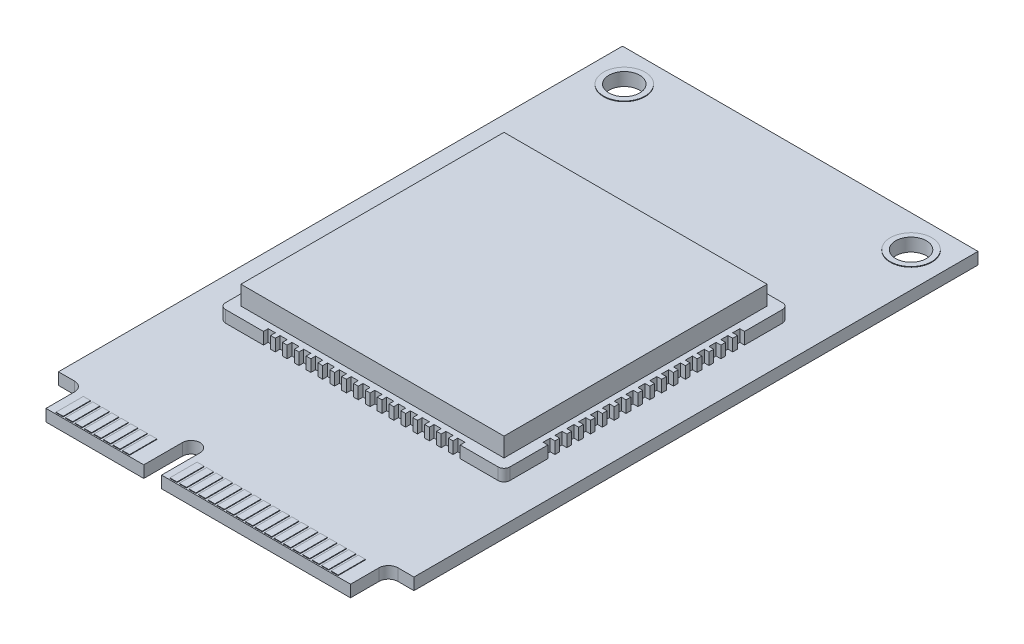
SolidWorks part; units mm, degrees
ref_plane "Front Plane" through (0, 0, 0) normal (0, 0, 1) x (1, 0, 0)
ref_plane "Top Plane" through (0, 0, 0) normal (0, 1, 0) x (1, 0, 0)
ref_plane "Right Plane" through (0, 0, 0) normal (1, 0, 0) x (0, 0, -1)
sketch "Sketch1" plane through (0, 0, 0) normal (0, 1, 0) x (1, 0, 0)
  line L0 (0, 23.8) -> (0, -48.0579) construction
  line L1 (-15, -23.8) -> (-13.65, -23.8)
  line L2 (-15, -23.8) -> (-15, 23.8)
  line L3 (-15, 23.8) -> (15, 23.8)
  line L4 (15, -23.8) -> (15, 23.8)
  line L5 (-15, -23.8) -> (15, 23.8) construction
  line L6 (-15, 23.8) -> (15, -23.8) construction
  line L8 (-12.85, -24.6) -> (-12.85, -27)
  line L9 (-12.85, -27) -> (-4.6, -27)
  line L10 (12.85, -24.6) -> (12.85, -27)
  line L11 (-3.85, -25.5051) -> (-3.85, -27) construction
  line L13 (-4.6, -27) -> (-4.6, -23.75)
  line L15 (-3.1, -27) -> (-3.1, -23.75)
  line L16 (13.65, -23.8) -> (15, -23.8)
  line L17 (-3.1, -27) -> (12.85, -27)
  arc A1 (-13.65, -23.8) -> (-12.85, -24.6) centre (-13.65, -24.6) cw
  arc A2 (13.65, -23.8) -> (12.85, -24.6) centre (13.65, -24.6) ccw
  arc A3 (-3.1, -23.75) -> (-4.6, -23.75) centre (-3.85, -23.75) ccw
  circle A5 centre (12.1, 21.05) radius 1.3
  circle A6 centre (-12.1, 21.05) radius 1.3
  point P0 (0, 0)
  point P27 (0, 0)
  point P28 (12.1, 21.5015)
  point P29 (0, 0)
  point P30 (-3.85, -23)
  dimension "D5" = 0.8
  dimension "D8" = 2.6
  dimension "D1" = 50.8
  dimension "D2" = 30
  dimension "D3" = 25.7
  dimension "D4" = 9
  dimension "D6" = 3.2
  dimension "D7" = 1.5
  dimension "D9" = 24.2
  dimension "D10" = 2.75
  dimension "D11" = 4
extrude "Boss-Extrude1" add sketch "Sketch1" along normal blind 1
sketch "Sketch2" plane through (0, 1, 0) normal (0, 1, 0) x (1, 0, 0)
  line L0 (-12.85, -27) -> (-4.6, -27) construction
  line L1 (-5.9, -26.9) -> (-6.5, -26.9)
  line L2 (-5.9, -26.9) -> (-5.9, -24.6)
  line L3 (-5.9, -24.6) -> (-6.5, -24.6)
  line L4 (-6.5, -26.9) -> (-6.5, -24.6)
  line L5 (-6.2, -24.6) -> (-6.2, -26.9) construction
  line L6 (-6.7, -26.9) -> (-6.7, -24.6)
  line L7 (-6.7, -26.9) -> (-7.3, -26.9)
  line L8 (-7.3, -26.9) -> (-7.3, -24.6)
  line L9 (-6.7, -24.6) -> (-7.3, -24.6)
  line L10 (-7.5, -26.9) -> (-7.5, -24.6)
  line L11 (-7.5, -26.9) -> (-8.1, -26.9)
  line L12 (-8.1, -26.9) -> (-8.1, -24.6)
  line L13 (-7.5, -24.6) -> (-8.1, -24.6)
  line L14 (-8.3, -26.9) -> (-8.3, -24.6)
  line L15 (-8.3, -26.9) -> (-8.9, -26.9)
  line L16 (-8.9, -26.9) -> (-8.9, -24.6)
  line L17 (-8.3, -24.6) -> (-8.9, -24.6)
  line L18 (-9.1, -26.9) -> (-9.1, -24.6)
  line L19 (-9.1, -26.9) -> (-9.7, -26.9)
  line L20 (-9.7, -26.9) -> (-9.7, -24.6)
  line L21 (-9.1, -24.6) -> (-9.7, -24.6)
  line L22 (-9.9, -26.9) -> (-9.9, -24.6)
  line L23 (-9.9, -26.9) -> (-10.5, -26.9)
  line L24 (-10.5, -26.9) -> (-10.5, -24.6)
  line L25 (-9.9, -24.6) -> (-10.5, -24.6)
  line L26 (-10.7, -26.9) -> (-10.7, -24.6)
  line L27 (-10.7, -26.9) -> (-11.3, -26.9)
  line L28 (-11.3, -26.9) -> (-11.3, -24.6)
  line L29 (-10.7, -24.6) -> (-11.3, -24.6)
  line L30 (-11.5, -26.9) -> (-11.5, -24.6)
  line L31 (-11.5, -26.9) -> (-12.1, -26.9)
  line L32 (-12.1, -26.9) -> (-12.1, -24.6)
  line L33 (-11.5, -24.6) -> (-12.1, -24.6)
  line L34 (-2.2, -24.6) -> (-2.2, -26.9) construction
  line L35 (-2.5, -26.9) -> (-1.9, -26.9)
  line L36 (-2.5, -26.9) -> (-2.5, -24.6)
  line L37 (-2.5, -24.6) -> (-1.9, -24.6)
  line L38 (-1.9, -26.9) -> (-1.9, -24.6)
  line L39 (-1.7, -26.9) -> (-1.7, -24.6)
  line L40 (-1.7, -26.9) -> (-1.1, -26.9)
  line L41 (-1.1, -26.9) -> (-1.1, -24.6)
  line L42 (-1.7, -24.6) -> (-1.1, -24.6)
  line L43 (-0.9, -26.9) -> (-0.9, -24.6)
  line L44 (-0.9, -26.9) -> (-0.3, -26.9)
  line L45 (-0.3, -26.9) -> (-0.3, -24.6)
  line L46 (-0.9, -24.6) -> (-0.3, -24.6)
  line L47 (-0.1, -26.9) -> (-0.1, -24.6)
  line L48 (-0.1, -26.9) -> (0.5, -26.9)
  line L49 (0.5, -26.9) -> (0.5, -24.6)
  line L50 (-0.1, -24.6) -> (0.5, -24.6)
  line L51 (0.7, -26.9) -> (0.7, -24.6)
  line L52 (0.7, -26.9) -> (1.3, -26.9)
  line L53 (1.3, -26.9) -> (1.3, -24.6)
  line L54 (0.7, -24.6) -> (1.3, -24.6)
  line L55 (1.5, -26.9) -> (1.5, -24.6)
  line L56 (1.5, -26.9) -> (2.1, -26.9)
  line L57 (2.1, -26.9) -> (2.1, -24.6)
  line L58 (1.5, -24.6) -> (2.1, -24.6)
  line L59 (2.3, -26.9) -> (2.3, -24.6)
  line L60 (2.3, -26.9) -> (2.9, -26.9)
  line L61 (2.9, -26.9) -> (2.9, -24.6)
  line L62 (2.3, -24.6) -> (2.9, -24.6)
  line L63 (3.1, -26.9) -> (3.1, -24.6)
  line L64 (3.1, -26.9) -> (3.7, -26.9)
  line L65 (3.7, -26.9) -> (3.7, -24.6)
  line L66 (3.1, -24.6) -> (3.7, -24.6)
  line L67 (3.9, -26.9) -> (3.9, -24.6)
  line L68 (3.9, -26.9) -> (4.5, -26.9)
  line L69 (4.5, -26.9) -> (4.5, -24.6)
  line L70 (3.9, -24.6) -> (4.5, -24.6)
  line L71 (4.7, -26.9) -> (4.7, -24.6)
  line L72 (4.7, -26.9) -> (5.3, -26.9)
  line L73 (5.3, -26.9) -> (5.3, -24.6)
  line L74 (4.7, -24.6) -> (5.3, -24.6)
  line L75 (5.5, -26.9) -> (5.5, -24.6)
  line L76 (5.5, -26.9) -> (6.1, -26.9)
  line L77 (6.1, -26.9) -> (6.1, -24.6)
  line L78 (5.5, -24.6) -> (6.1, -24.6)
  line L79 (6.3, -26.9) -> (6.3, -24.6)
  line L80 (6.3, -26.9) -> (6.9, -26.9)
  line L81 (6.9, -26.9) -> (6.9, -24.6)
  line L82 (6.3, -24.6) -> (6.9, -24.6)
  line L83 (7.1, -26.9) -> (7.1, -24.6)
  line L84 (7.1, -26.9) -> (7.7, -26.9)
  line L85 (7.7, -26.9) -> (7.7, -24.6)
  line L86 (7.1, -24.6) -> (7.7, -24.6)
  line L87 (7.9, -26.9) -> (7.9, -24.6)
  line L88 (7.9, -26.9) -> (8.5, -26.9)
  line L89 (8.5, -26.9) -> (8.5, -24.6)
  line L90 (7.9, -24.6) -> (8.5, -24.6)
  line L91 (8.7, -26.9) -> (8.7, -24.6)
  line L92 (8.7, -26.9) -> (9.3, -26.9)
  line L93 (9.3, -26.9) -> (9.3, -24.6)
  line L94 (8.7, -24.6) -> (9.3, -24.6)
  line L95 (9.5, -26.9) -> (9.5, -24.6)
  line L96 (9.5, -26.9) -> (10.1, -26.9)
  line L97 (10.1, -26.9) -> (10.1, -24.6)
  line L98 (9.5, -24.6) -> (10.1, -24.6)
  line L99 (10.3, -26.9) -> (10.3, -24.6)
  line L100 (10.3, -26.9) -> (10.9, -26.9)
  line L101 (10.9, -26.9) -> (10.9, -24.6)
  line L102 (10.3, -24.6) -> (10.9, -24.6)
  line L103 (11.1, -26.9) -> (11.1, -24.6)
  line L104 (11.1, -26.9) -> (11.7, -26.9)
  line L105 (11.7, -26.9) -> (11.7, -24.6)
  line L106 (11.1, -24.6) -> (11.7, -24.6)
  arc A0 (-3.1, -23.75) -> (-4.6, -23.75) centre (-3.85, -23.75) ccw construction
  circle A1 centre (-12.1, 21.05) radius 1.3 construction
  circle A2 centre (-12.1, 21.05) radius 1.3
  circle A3 centre (-12.1, 21.05) radius 1.75
  circle A4 centre (12.1, 21.05) radius 1.75
  circle A5 centre (12.1, 21.05) radius 1.3 construction
  circle A6 centre (12.1, 21.05) radius 1.3
  point P11 (-3.85, -23)
  dimension "D8" = 3.5
  dimension "D1" = 2.3
  dimension "D2" = 0.6
  dimension "D3" = 0.1
  dimension "D4" = 2.35
  dimension "D6" = 4
  dimension "D5" = 8
  dimension "D7" = 18
extrude "Boss-Extrude2" add sketch "Sketch2" along normal blind 0.05
ref_plane "Plane1" through (0, 0.5, 0) normal (0, 1, 0) x (1, 0, 0)
mirror "Mirror1" about plane through (0, 0.5, 0) normal (0, 1, 0) of "Boss-Extrude2"
sketch "Sketch3" plane through (0, 1, 0) normal (0, 1, 0) x (1, 0, 0)
  line L0 (0, 23.8) -> (0, -21.0552) construction
  line L1 (-11.5, 10.8) -> (-8.3, 10.8)
  line L2 (-12, 10.3) -> (-12, 7.1)
  line L3 (-11.5, -13.2) -> (-8.3, -13.2)
  line L4 (12, 10.3) -> (12, 7.1)
  line L5 (15, 23.8) -> (-15, 23.8) construction
  line L6 (-8.3, -13.2) -> (-8.3, -12.8)
  line L7 (-8.3, -12.8) -> (-7.7, -12.8)
  line L8 (-7.7, -12.8) -> (-7.7, -13.2)
  line L9 (-7.7, -13.2) -> (-7.3, -13.2)
  line L10 (-8, -12.8) -> (-8, -11.628) construction
  line L11 (-7.3, -13.2) -> (-7.3, -12.8)
  line L12 (-7.3, -12.8) -> (-6.7, -12.8)
  line L13 (-6.7, -12.8) -> (-6.7, -13.2)
  line L14 (-6.3, -13.2) -> (-6.3, -12.8)
  line L15 (-6.3, -12.8) -> (-5.7, -12.8)
  line L16 (-5.7, -12.8) -> (-5.7, -13.2)
  line L17 (-5.3, -13.2) -> (-5.3, -12.8)
  line L18 (-5.3, -12.8) -> (-4.7, -12.8)
  line L19 (-4.7, -12.8) -> (-4.7, -13.2)
  line L20 (-4.3, -13.2) -> (-4.3, -12.8)
  line L21 (-4.3, -12.8) -> (-3.7, -12.8)
  line L22 (-3.7, -12.8) -> (-3.7, -13.2)
  line L23 (-3.3, -13.2) -> (-3.3, -12.8)
  line L24 (-3.3, -12.8) -> (-2.7, -12.8)
  line L25 (-2.7, -12.8) -> (-2.7, -13.2)
  line L26 (-2.3, -13.2) -> (-2.3, -12.8)
  line L27 (-2.3, -12.8) -> (-1.7, -12.8)
  line L28 (-1.7, -12.8) -> (-1.7, -13.2)
  line L29 (-1.3, -13.2) -> (-1.3, -12.8)
  line L30 (-1.3, -12.8) -> (-0.7, -12.8)
  line L31 (-0.7, -12.8) -> (-0.7, -13.2)
  line L32 (-0.3, -13.2) -> (-0.3, -12.8)
  line L33 (-0.3, -12.8) -> (0.3, -12.8)
  line L34 (0.3, -12.8) -> (0.3, -13.2)
  line L35 (0.7, -13.2) -> (0.7, -12.8)
  line L36 (0.7, -12.8) -> (1.3, -12.8)
  line L37 (1.3, -12.8) -> (1.3, -13.2)
  line L38 (1.7, -13.2) -> (1.7, -12.8)
  line L39 (1.7, -12.8) -> (2.3, -12.8)
  line L40 (2.3, -12.8) -> (2.3, -13.2)
  line L41 (2.7, -13.2) -> (2.7, -12.8)
  line L42 (2.7, -12.8) -> (3.3, -12.8)
  line L43 (3.3, -12.8) -> (3.3, -13.2)
  line L44 (3.7, -13.2) -> (3.7, -12.8)
  line L45 (3.7, -12.8) -> (4.3, -12.8)
  line L46 (4.3, -12.8) -> (4.3, -13.2)
  line L47 (4.7, -13.2) -> (4.7, -12.8)
  line L48 (4.7, -12.8) -> (5.3, -12.8)
  line L49 (5.3, -12.8) -> (5.3, -13.2)
  line L50 (5.7, -13.2) -> (5.7, -12.8)
  line L51 (5.7, -12.8) -> (6.3, -12.8)
  line L52 (6.3, -12.8) -> (6.3, -13.2)
  line L53 (6.7, -13.2) -> (6.7, -12.8)
  line L54 (6.7, -12.8) -> (7.3, -12.8)
  line L55 (7.3, -12.8) -> (7.3, -13.2)
  line L56 (7.7, -13.2) -> (7.7, -12.8)
  line L57 (7.7, -12.8) -> (8.3, -12.8)
  line L58 (8.3, -12.8) -> (8.3, -13.2)
  line L59 (-5.7, -13.2) -> (-5.3, -13.2)
  line L60 (-6.7, -13.2) -> (-6.3, -13.2)
  line L61 (-4.7, -13.2) -> (-4.3, -13.2)
  line L62 (-1.7, -13.2) -> (-1.3, -13.2)
  line L63 (-0.7, -13.2) -> (-0.3, -13.2)
  line L64 (0.3, -13.2) -> (0.7, -13.2)
  line L65 (1.3, -13.2) -> (1.7, -13.2)
  line L66 (2.3, -13.2) -> (2.7, -13.2)
  line L67 (3.3, -13.2) -> (3.7, -13.2)
  line L68 (4.3, -13.2) -> (4.7, -13.2)
  line L69 (5.3, -13.2) -> (5.7, -13.2)
  line L70 (6.3, -13.2) -> (6.7, -13.2)
  line L71 (7.3, -13.2) -> (7.7, -13.2)
  line L72 (8.3, -13.2) -> (11.5, -13.2)
  line L74 (-12, 7.1) -> (-11.6, 7.1)
  line L75 (-11.6, 7.1) -> (-11.6, 6.5)
  line L76 (-11.6, 6.5) -> (-12, 6.5)
  line L77 (-12, 6.1) -> (-11.6, 6.1)
  line L78 (-11.6, 6.1) -> (-11.6, 5.5)
  line L79 (-11.6, 5.5) -> (-12, 5.5)
  line L80 (-12, 5.1) -> (-11.6, 5.1)
  line L81 (-11.6, 5.1) -> (-11.6, 4.5)
  line L82 (-11.6, 4.5) -> (-12, 4.5)
  line L83 (-12, 4.1) -> (-11.6, 4.1)
  line L84 (-11.6, 3.5) -> (-12, 3.5)
  line L85 (-11.6, 4.1) -> (-11.6, 3.5)
  line L86 (-12, 3.1) -> (-11.6, 3.1)
  line L87 (-11.6, 3.1) -> (-11.6, 2.5)
  line L88 (-11.6, 2.5) -> (-12, 2.5)
  line L89 (-12, 2.1) -> (-11.6, 2.1)
  line L90 (-11.6, 2.1) -> (-11.6, 1.5)
  line L91 (-11.6, 1.5) -> (-12, 1.5)
  line L92 (-12, 1.1) -> (-11.6, 1.1)
  line L93 (-11.6, 1.1) -> (-11.6, 0.5)
  line L94 (-11.6, 0.5) -> (-12, 0.5)
  line L95 (-12, 0.1) -> (-11.6, 0.1)
  line L96 (-11.6, 0.1) -> (-11.6, -0.5)
  line L97 (-11.6, -0.5) -> (-12, -0.5)
  line L98 (-12, -0.9) -> (-11.6, -0.9)
  line L99 (-11.6, -0.9) -> (-11.6, -1.5)
  line L100 (-11.6, -1.5) -> (-12, -1.5)
  line L101 (-12, -1.9) -> (-11.6, -1.9)
  line L102 (-11.6, -1.9) -> (-11.6, -2.5)
  line L103 (-12, -2.9) -> (-11.6, -2.9)
  line L104 (-11.6, -2.9) -> (-11.6, -3.5)
  line L105 (-11.6, -3.5) -> (-12, -3.5)
  line L106 (-11.6, -4.5) -> (-12, -4.5)
  line L107 (-12, -3.9) -> (-11.6, -3.9)
  line L108 (-11.6, -3.9) -> (-11.6, -4.5)
  line L109 (-12, -4.9) -> (-11.6, -4.9)
  line L110 (-11.6, -4.9) -> (-11.6, -5.5)
  line L111 (-11.6, -5.5) -> (-12, -5.5)
  line L112 (-11.6, -2.5) -> (-12, -2.5)
  line L113 (-12, -5.9) -> (-11.6, -5.9)
  line L114 (-11.6, -5.9) -> (-11.6, -6.5)
  line L115 (-11.6, -6.5) -> (-12, -6.5)
  line L116 (-12, -6.9) -> (-11.6, -6.9)
  line L117 (-11.6, -7.5) -> (-12, -7.5)
  line L118 (-11.6, -6.9) -> (-11.6, -7.5)
  line L119 (-11.6, -7.9) -> (-11.6, -8.5)
  line L120 (-12, -7.9) -> (-11.6, -7.9)
  line L121 (-11.6, -9.5) -> (-12, -9.5)
  line L122 (-11.6, -8.9) -> (-11.6, -9.5)
  line L123 (-11.6, -8.5) -> (-12, -8.5)
  line L124 (-12, -8.9) -> (-11.6, -8.9)
  line L125 (8.3, 10.8) -> (8.3, 10.4)
  line L126 (8.3, 10.4) -> (7.7, 10.4)
  line L127 (7.7, 10.4) -> (7.7, 10.8)
  line L128 (7.3, 10.8) -> (7.3, 10.4)
  line L129 (7.3, 10.4) -> (6.7, 10.4)
  line L130 (6.7, 10.4) -> (6.7, 10.8)
  line L131 (6.3, 10.8) -> (6.3, 10.4)
  line L132 (6.3, 10.4) -> (5.7, 10.4)
  line L133 (5.7, 10.4) -> (5.7, 10.8)
  line L134 (5.3, 10.8) -> (5.3, 10.4)
  line L135 (4.7, 10.4) -> (4.7, 10.8)
  line L136 (5.3, 10.4) -> (4.7, 10.4)
  line L137 (4.3, 10.8) -> (4.3, 10.4)
  line L138 (4.3, 10.4) -> (3.7, 10.4)
  line L139 (3.7, 10.4) -> (3.7, 10.8)
  line L140 (3.3, 10.8) -> (3.3, 10.4)
  line L141 (3.3, 10.4) -> (2.7, 10.4)
  line L142 (2.7, 10.4) -> (2.7, 10.8)
  line L143 (2.3, 10.8) -> (2.3, 10.4)
  line L144 (2.3, 10.4) -> (1.7, 10.4)
  line L145 (1.7, 10.4) -> (1.7, 10.8)
  line L146 (1.3, 10.8) -> (1.3, 10.4)
  line L147 (1.3, 10.4) -> (0.7, 10.4)
  line L148 (0.7, 10.4) -> (0.7, 10.8)
  line L149 (0.3, 10.8) -> (0.3, 10.4)
  line L150 (0.3, 10.4) -> (-0.3, 10.4)
  line L151 (-0.3, 10.4) -> (-0.3, 10.8)
  line L152 (-0.7, 10.8) -> (-0.7, 10.4)
  line L153 (-0.7, 10.4) -> (-1.3, 10.4)
  line L154 (-1.7, 10.8) -> (-1.7, 10.4)
  line L155 (-1.7, 10.4) -> (-2.3, 10.4)
  line L156 (-2.3, 10.4) -> (-2.3, 10.8)
  line L157 (-3.3, 10.4) -> (-3.3, 10.8)
  line L158 (-2.7, 10.8) -> (-2.7, 10.4)
  line L159 (-2.7, 10.4) -> (-3.3, 10.4)
  line L160 (-3.7, 10.8) -> (-3.7, 10.4)
  line L161 (-3.7, 10.4) -> (-4.3, 10.4)
  line L162 (-4.3, 10.4) -> (-4.3, 10.8)
  line L163 (-1.3, 10.4) -> (-1.3, 10.8)
  line L164 (-4.7, 10.8) -> (-4.7, 10.4)
  line L165 (-4.7, 10.4) -> (-5.3, 10.4)
  line L166 (-5.3, 10.4) -> (-5.3, 10.8)
  line L167 (-5.7, 10.8) -> (-5.7, 10.4)
  line L168 (-6.3, 10.4) -> (-6.3, 10.8)
  line L169 (-5.7, 10.4) -> (-6.3, 10.4)
  line L170 (-6.7, 10.4) -> (-7.3, 10.4)
  line L171 (-6.7, 10.8) -> (-6.7, 10.4)
  line L172 (-8.3, 10.4) -> (-8.3, 10.8)
  line L173 (-7.7, 10.4) -> (-8.3, 10.4)
  line L174 (-7.3, 10.4) -> (-7.3, 10.8)
  line L175 (-7.7, 10.8) -> (-7.7, 10.4)
  line L176 (12, -9.5) -> (11.6, -9.5)
  line L177 (11.6, -9.5) -> (11.6, -8.9)
  line L178 (11.6, -8.9) -> (12, -8.9)
  line L179 (12, -8.5) -> (11.6, -8.5)
  line L180 (11.6, -8.5) -> (11.6, -7.9)
  line L181 (11.6, -7.9) -> (12, -7.9)
  line L182 (12, -7.5) -> (11.6, -7.5)
  line L183 (11.6, -7.5) -> (11.6, -6.9)
  line L184 (11.6, -6.9) -> (12, -6.9)
  line L185 (12, -6.5) -> (11.6, -6.5)
  line L186 (11.6, -5.9) -> (12, -5.9)
  line L187 (11.6, -6.5) -> (11.6, -5.9)
  line L188 (12, -5.5) -> (11.6, -5.5)
  line L189 (11.6, -5.5) -> (11.6, -4.9)
  line L190 (11.6, -4.9) -> (12, -4.9)
  line L191 (12, -4.5) -> (11.6, -4.5)
  line L192 (11.6, -4.5) -> (11.6, -3.9)
  line L193 (11.6, -3.9) -> (12, -3.9)
  line L194 (12, -3.5) -> (11.6, -3.5)
  line L195 (11.6, -3.5) -> (11.6, -2.9)
  line L196 (11.6, -2.9) -> (12, -2.9)
  line L197 (12, -2.5) -> (11.6, -2.5)
  line L198 (11.6, -2.5) -> (11.6, -1.9)
  line L199 (11.6, -1.9) -> (12, -1.9)
  line L200 (12, -1.5) -> (11.6, -1.5)
  line L201 (11.6, -1.5) -> (11.6, -0.9)
  line L202 (11.6, -0.9) -> (12, -0.9)
  line L203 (12, -0.5) -> (11.6, -0.5)
  line L204 (11.6, -0.5) -> (11.6, 0.1)
  line L205 (12, 0.5) -> (11.6, 0.5)
  line L206 (11.6, 0.5) -> (11.6, 1.1)
  line L207 (11.6, 1.1) -> (12, 1.1)
  line L208 (11.6, 2.1) -> (12, 2.1)
  line L209 (12, 1.5) -> (11.6, 1.5)
  line L210 (11.6, 1.5) -> (11.6, 2.1)
  line L211 (12, 2.5) -> (11.6, 2.5)
  line L212 (11.6, 2.5) -> (11.6, 3.1)
  line L213 (11.6, 3.1) -> (12, 3.1)
  line L214 (11.6, 0.1) -> (12, 0.1)
  line L215 (12, 3.5) -> (11.6, 3.5)
  line L216 (11.6, 3.5) -> (11.6, 4.1)
  line L217 (11.6, 4.1) -> (12, 4.1)
  line L218 (12, 4.5) -> (11.6, 4.5)
  line L219 (11.6, 5.1) -> (12, 5.1)
  line L220 (11.6, 4.5) -> (11.6, 5.1)
  line L221 (11.6, 5.5) -> (11.6, 6.1)
  line L222 (12, 5.5) -> (11.6, 5.5)
  line L223 (11.6, 7.1) -> (12, 7.1)
  line L224 (11.6, 6.5) -> (11.6, 7.1)
  line L225 (11.6, 6.1) -> (12, 6.1)
  line L226 (12, 6.5) -> (11.6, 6.5)
  line L227 (-3.7, -13.2) -> (-3.3, -13.2)
  line L228 (-2.7, -13.2) -> (-2.3, -13.2)
  line L229 (12, -9.5) -> (12, -12.7)
  line L230 (12, -8.5) -> (12, -8.9)
  line L231 (12, -7.5) -> (12, -7.9)
  line L232 (12, -6.5) -> (12, -6.9)
  line L233 (12, -4.5) -> (12, -4.9)
  line L234 (12, -5.5) -> (12, -5.9)
  line L235 (12, -3.5) -> (12, -3.9)
  line L236 (12, -1.5) -> (12, -1.9)
  line L237 (12, -0.5) -> (12, -0.9)
  line L238 (12, 0.5) -> (12, 0.1)
  line L239 (12, 1.5) -> (12, 1.1)
  line L240 (12, 2.5) -> (12, 2.1)
  line L241 (12, 4.5) -> (12, 3.1)
  line L242 (12, 5.5) -> (12, 5.1)
  line L243 (12, 6.5) -> (12, 6.1)
  line L244 (12, -2.5) -> (12, -2.9)
  line L245 (8.3, 10.8) -> (11.5, 10.8)
  line L246 (7.3, 10.8) -> (7.7, 10.8)
  line L247 (6.3, 10.8) -> (6.7, 10.8)
  line L248 (5.3, 10.8) -> (5.7, 10.8)
  line L249 (4.3, 10.8) -> (4.7, 10.8)
  line L250 (3.3, 10.8) -> (3.7, 10.8)
  line L251 (2.3, 10.8) -> (2.7, 10.8)
  line L252 (1.3, 10.8) -> (1.7, 10.8)
  line L253 (0.3, 10.8) -> (0.7, 10.8)
  line L254 (-0.7, 10.8) -> (-0.3, 10.8)
  line L255 (-1.7, 10.8) -> (-1.3, 10.8)
  line L256 (-2.7, 10.8) -> (-2.3, 10.8)
  line L257 (-3.7, 10.8) -> (-3.3, 10.8)
  line L258 (-4.7, 10.8) -> (-4.3, 10.8)
  line L259 (-5.7, 10.8) -> (-5.3, 10.8)
  line L260 (-6.7, 10.8) -> (-6.3, 10.8)
  line L261 (-7.7, 10.8) -> (-7.3, 10.8)
  line L262 (-12, 6.5) -> (-12, 6.1)
  line L263 (-12, 5.5) -> (-12, 5.1)
  line L264 (-12, 4.5) -> (-12, 4.1)
  line L265 (-12, 3.5) -> (-12, 3.1)
  line L266 (-12, 2.5) -> (-12, 2.1)
  line L267 (-12, 1.5) -> (-12, 1.1)
  line L268 (-12, 0.5) -> (-12, 0.1)
  line L269 (-12, -1.5) -> (-12, -1.9)
  line L270 (-12, -2.5) -> (-12, -2.9)
  line L271 (-12, -3.5) -> (-12, -3.9)
  line L272 (-12, -0.5) -> (-12, -0.9)
  line L273 (-12, -4.5) -> (-12, -4.9)
  line L274 (-12, -5.5) -> (-12, -5.9)
  line L275 (-12, -6.5) -> (-12, -6.9)
  line L276 (-12, -7.5) -> (-12, -7.9)
  line L277 (-12, -8.5) -> (-12, -8.9)
  line L278 (-12, -9.5) -> (-12, -12.7)
  arc A0 (11.5, 10.8) -> (12, 10.3) centre (11.5, 10.3) cw
  arc A1 (-11.5, 10.8) -> (-12, 10.3) centre (-11.5, 10.3) ccw
  arc A2 (11.5, -13.2) -> (12, -12.7) centre (11.5, -12.7) ccw
  arc A3 (-12, -12.7) -> (-11.5, -13.2) centre (-11.5, -12.7) ccw
  point P11 (12, 10.8)
  point P14 (-12, 10.8)
  point P91 (0, 0.5792)
  point P299 (0, -1.2)
  dimension "D2" = 0.5
  dimension "D3" = 0.5
  dimension "D1" = 24
  dimension "D4" = 0.6
  dimension "D5" = 0.4
  dimension "D6" = 4
  dimension "D9" = 13
  dimension "D7" = 17
  dimension "D8" = 4
extrude "Boss-Extrude3" add sketch "Sketch3" along normal blind 1 contours L278 A3 L3 L6 L7 L8 L9 L11 L12 L13 L60 L14 L15 L16 L59 L17 L18 L19 L61 L20 L21 L22 L227 L23 L24 L25 L228 L26 L27 L28 L62 L29 L30 L31 L63 L32 L33 L34 L64 L35 L36 L37 L65 L38 L39 L40 L66 L41 L42 L43 L67 region at (0, 1, 1.2)
sketch "Sketch4" plane through (0, 2, 0) normal (0, 1, 0) x (1, 0, 0)
  line L0 (-11.5, 10.3) -> (11.5, -12.7) construction
  line L1 (11.5, 10.3) -> (-11.5, -12.7) construction
  line L3 (-11.1, 9.9) -> (11.1, 9.9)
  line L4 (-11.1, 9.9) -> (-11.1, -12.3)
  line L5 (-11.1, -12.3) -> (11.1, -12.3)
  line L6 (11.1, 9.9) -> (11.1, -12.3)
  line L7 (-11.1, 9.9) -> (11.1, -12.3) construction
  line L8 (-11.1, -12.3) -> (11.1, 9.9) construction
  point P8 (0, -1.2)
  dimension "D1" = 22.2
extrude "Boss-Extrude4" add sketch "Sketch4" along normal blind 1.6
